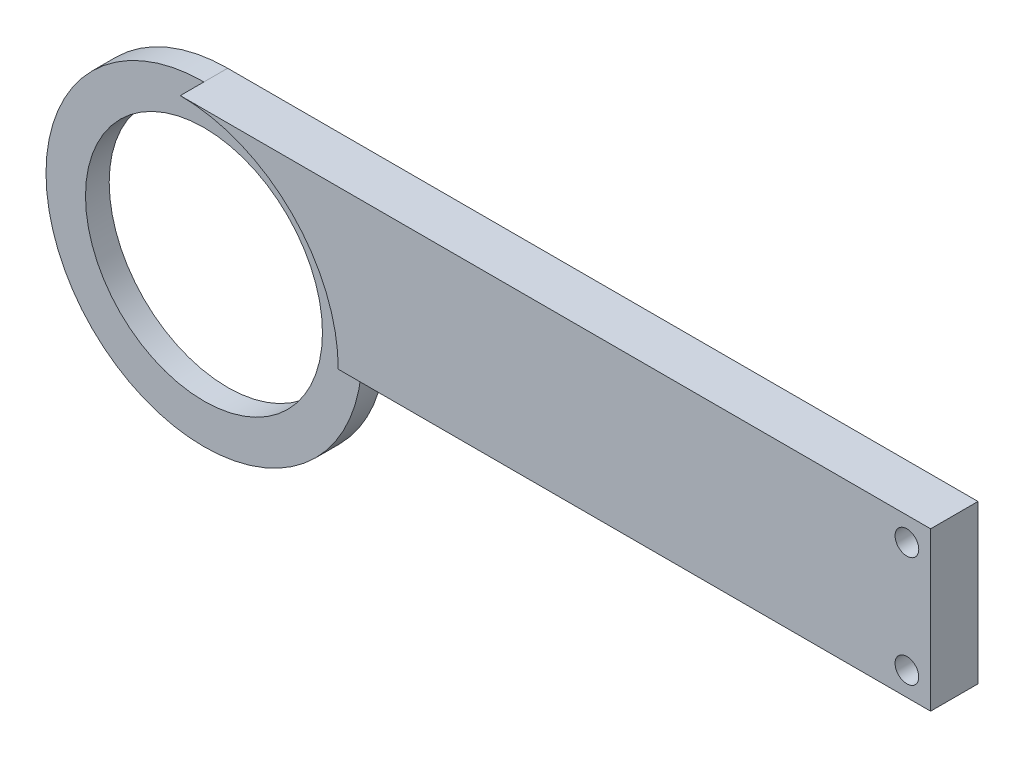
SolidWorks part; units mm, degrees
ref_plane "Plan de face" through (0, 0, 0) normal (0, 0, 1) x (1, 0, 0)
ref_plane "Plan de dessus" through (0, 0, 0) normal (0, 1, 0) x (1, 0, 0)
ref_plane "Plan de droite" through (0, 0, 0) normal (1, 0, 0) x (0, 0, -1)
sketch "Esquisse1" plane through (0, 0, 0) normal (0, 0, 1) x (1, 0, 0)
  line L1 (42.6139, 23.7864) -> (-43.2113, 23.7864)
  line L2 (42.6139, 23.7864) -> (42.6139, 3.7864)
  line L3 (42.6139, 3.7864) -> (-43.2113, 3.7864)
  line L4 (-43.2113, 23.7864) -> (-43.2113, 3.7864)
  circle A0 centre (-43.2113, 3.7864) radius 20
  circle A1 centre (-43.2113, 3.7864) radius 15
  dimension "D2" = 0
  dimension "D3" = 40
  dimension "D1" = 20
extrude "Boss.-Extru.1" add sketch "Esquisse1" along normal blind 6 contours A0 L3 L2 L1 | A1 L4 A0 L3 | A1 L3 A0 L4 region at (7.4132, 14.1251, 0) region at (-31.9947, 15.003, 0) region at (-43.777, 21.2864, 0)
sketch "Esquisse2" plane through (0, 0, 6) normal (0, 0, 1) x (1, 0, 0)
  circle A0 centre (-43.2113, 3.7864) radius 15
  circle A1 centre (-43.2113, 3.7864) radius 15 construction
  circle A2 centre (-43.2113, 3.7864) radius 20
  dimension "D1" = 30
  dimension "D2" = 0
extrude "Enlèv. mat.-Extru.1" cut sketch "Esquisse2" against normal blind 3
sketch "Esquisse3" plane through (0, 0, 6) normal (0, 0, 1) x (1, 0, 0)
  line L1 (42.6139, 23.7864) -> (51.7839, 23.7864)
  line L2 (42.6139, 23.7864) -> (42.6139, 3.7864)
  line L3 (42.6139, 3.7864) -> (51.7839, 3.7864)
  line L4 (51.7839, 23.7864) -> (51.7839, 3.7864)
  dimension "D1" = 20
  dimension "D2" = 9.17
extrude "Boss.-Extru.2" add sketch "Esquisse3" against normal blind 6
sketch "Esquisse4" plane through (0, 0, 0) normal (0, 0, -1) x (-1, 0, 0)
  line L0 (-48.7839, 31.2142) -> (-48.7839, -14.3241) construction
  line L1 (-51.7839, 3.7864) -> (-51.7839, 23.7864) construction
  line L2 (-51.7839, 3.7864) -> (23.2113, 3.7864) construction
  line L3 (-51.7839, 23.7864) -> (43.2113, 23.7864) construction
  circle A0 centre (-48.7839, 20.7864) radius 1.5
  circle A1 centre (-48.7839, 6.7864) radius 1.5
  dimension "D1" = 3
  dimension "D2" = 3
  dimension "D4" = 3
  dimension "D5" = 3
  dimension "D3" = 3
extrude "Enlèv. mat.-Extru.2" cut sketch "Esquisse4" against normal blind 10
